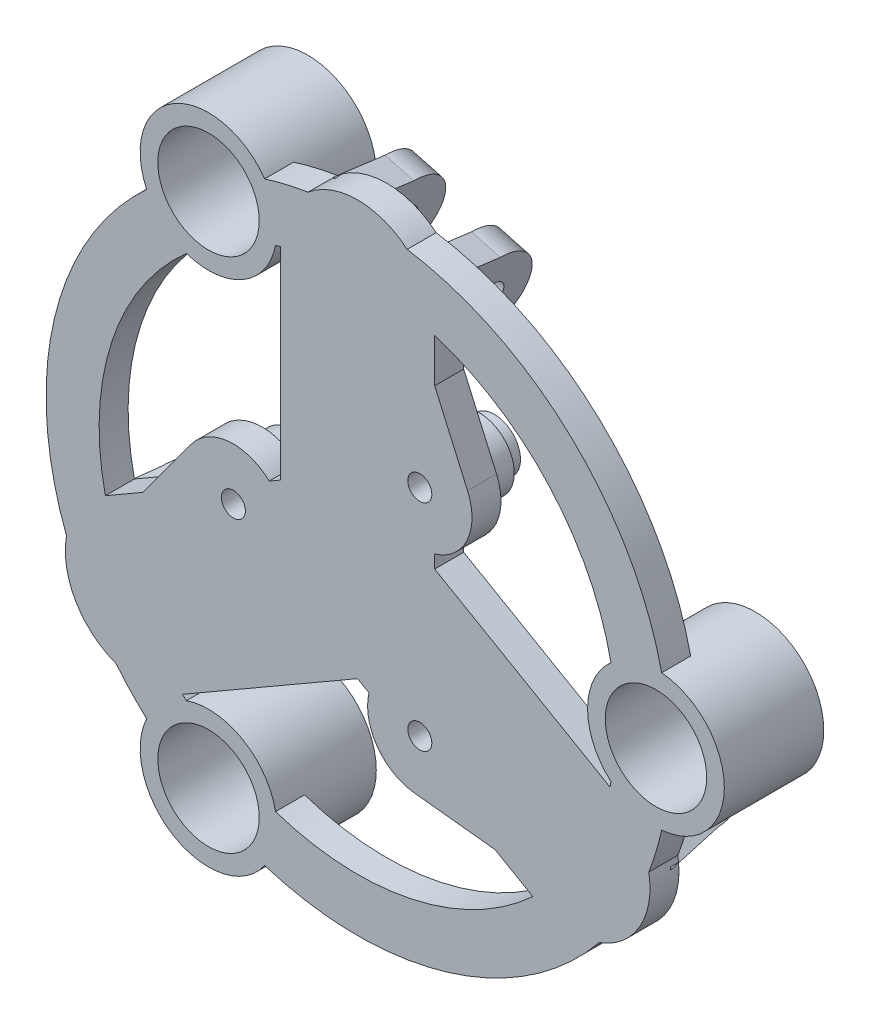
SolidWorks part; units mm, degrees
ref_plane "Front Plane" through (0, 0, 0) normal (0, 0, 1) x (1, 0, 0)
ref_plane "Top Plane" through (0, 0, 0) normal (0, 1, 0) x (1, 0, 0)
ref_plane "Right Plane" through (0, 0, 0) normal (1, 0, 0) x (0, 0, -1)
sketch "S01 - Joining centre of floating Y" plane through (0, 0, 0) normal (0, 0, 1) x (1, 0, 0)
  circle A0 centre (0, 0) radius 9
  dimension "D1" = 18
extrude "01 - Joining centre of floating Y" add sketch "S01 - Joining centre of floating Y" along normal blind 3.5 from offset 33.5
sketch "S02 - Floating spoke 1" plane through (0, 0, 0) normal (0, 0, 1) x (1, 0, 0)
  line L0 (4.65, -8.054) -> (-21.3308, -23.054)
  line L1 (-30.6308, -6.946) -> (-4.65, 8.054)
  arc A0 (-21.3308, -23.054) -> (-30.6308, -6.946) centre (-25.9808, -15) cw
  arc A1 (-4.65, 8.054) -> (4.65, -8.054) centre (0, 0) cw
  dimension "D1" = 9.3
  dimension "D2" = 9.3
  dimension "D3" = 4.65
  dimension "D4" = 4.65
  dimension "D5" = 21.3308
  dimension "D6" = 25.9808
  dimension "D7" = 30.6308
  dimension "D8" = 6.946
extrude "02 - Floating spoke 1" add sketch "S02 - Floating spoke 1" along normal blind 3.5 from offset 33.5
sketch "S03 - Floating spoke 2" plane through (0, 0, 0) normal (0, 0, 1) x (1, 0, 0)
  line L0 (4.65, 8.054) -> (30.6308, -6.946)
  line L1 (21.3308, -23.054) -> (-4.65, -8.054)
  arc A0 (30.6308, -6.946) -> (21.3308, -23.054) centre (25.9808, -15) cw
  arc A1 (-4.65, -8.054) -> (4.65, 8.054) centre (0, 0) cw
  dimension "D1" = 9.3
  dimension "D2" = 9.3
  dimension "D3" = 4.65
  dimension "D4" = 21.3308
  dimension "D5" = 25.9808
  dimension "D6" = 30.6308
  dimension "D7" = 4.65
  dimension "D8" = 6.946
extrude "03 - Floating spoke 2" add sketch "S03 - Floating spoke 2" along normal blind 3.5 from offset 33.5
sketch "S04 - Floating spoke 3" plane through (0, 0, 0) normal (0, 0, 1) x (1, 0, 0)
  line L0 (-9.3, 0) -> (-9.3, 30)
  line L1 (9.3, 30) -> (9.3, 0)
  arc A0 (-9.3, 30) -> (9.3, 30) centre (0, 30) cw
  arc A1 (9.3, 0) -> (-9.3, 0) centre (0, 0) cw
  dimension "D1" = 9.3
  dimension "D2" = 30
extrude "04 - Floating spoke 3" add sketch "S04 - Floating spoke 3" along normal blind 3.5 from offset 33.5
sketch "S05 - Moving tendon tie web 1" plane through (0, 0, 0) normal (0, 0, 1) x (1, 0, 0)
  line L0 (25.2997, -21.2631) -> (6.8189, -19.2535)
  line L1 (8.1811, -6.7273) -> (26.6618, -8.7369)
  arc A0 (6.8189, -19.2535) -> (8.1811, -6.7273) centre (7.5, -12.9904) cw
  arc A1 (26.6618, -8.7369) -> (25.2997, -21.2631) centre (25.9808, -15) cw
  dimension "D1" = 6.3
  dimension "D2" = 6.3
  dimension "D3" = 6.8189
  dimension "D4" = 7.5
  dimension "D5" = 8.1811
  dimension "D6" = 25.2997
  dimension "D7" = 25.9808
  dimension "D8" = 26.6618
  dimension "D9" = 6.7273
  dimension "D10" = 8.7369
extrude "05 - Moving tendon tie web 1" add sketch "S05 - Moving tendon tie web 1" along normal blind 3.5 from offset 33.5
sketch "S06 - Tendon anchor base 1" plane through (0, 0, 0) normal (0, 0, 1) x (1, 0, 0)
  circle A0 centre (7.5, -12.9904) radius 4.2
  dimension "D1" = 8.4
  dimension "D2" = 7.5
  dimension "D3" = 12.9904
extrude "06 - Tendon anchor base 1" add sketch "S06 - Tendon anchor base 1" along normal blind 3.7 from offset 29.8
sketch "S07 - Tendon mouth 1" plane through (0, 0, 0) normal (0, 0, 1) x (1, 0, 0)
  circle A0 centre (7.5, -12.9904) radius 3.15
  dimension "D1" = 6.3
  dimension "D2" = 7.5
  dimension "D3" = 12.9904
extrude "07 - Tendon mouth 1" add sketch "S07 - Tendon mouth 1" along normal blind 1.8 from offset 28
sketch "S08 - Moving tendon tie web 2" plane through (0, 0, 0) normal (0, 0, 1) x (1, 0, 0)
  line L0 (5.7645, 32.5417) -> (13.2645, 15.5321)
  line L1 (1.7355, 10.4487) -> (-5.7645, 27.4583)
  arc A0 (13.2645, 15.5321) -> (1.7355, 10.4487) centre (7.5, 12.9904) cw
  arc A1 (-5.7645, 27.4583) -> (5.7645, 32.5417) centre (0, 30) cw
  dimension "D1" = 6.3
  dimension "D2" = 6.3
  dimension "D3" = 1.7355
  dimension "D4" = 5.7645
  dimension "D5" = 7.5
  dimension "D6" = 13.2645
  dimension "D7" = 5.7645
  dimension "D8" = 10.4487
  dimension "D9" = 27.4583
extrude "08 - Moving tendon tie web 2" add sketch "S08 - Moving tendon tie web 2" along normal blind 3.5 from offset 33.5
sketch "S09 - Tendon anchor base 2" plane through (0, 0, 0) normal (0, 0, 1) x (1, 0, 0)
  circle A0 centre (7.5, 12.9904) radius 4.2
  dimension "D1" = 8.4
  dimension "D2" = 7.5
  dimension "D3" = 12.9904
extrude "09 - Tendon anchor base 2" add sketch "S09 - Tendon anchor base 2" along normal blind 3.7 from offset 29.8
sketch "S10 - Tendon mouth 2" plane through (0, 0, 0) normal (0, 0, 1) x (1, 0, 0)
  circle A0 centre (7.5, 12.9904) radius 3.15
  dimension "D1" = 6.3
  dimension "D2" = 7.5
  dimension "D3" = 12.9904
extrude "10 - Tendon mouth 2" add sketch "S10 - Tendon mouth 2" along normal blind 1.8 from offset 28
sketch "S11 - Moving tendon tie web 3" plane through (0, 0, 0) normal (0, 0, 1) x (1, 0, 0)
  line L0 (-31.0642, -11.2786) -> (-20.0835, 3.7214)
  line L1 (-9.9165, -3.7214) -> (-20.8973, -18.7214)
  arc A0 (-20.0835, 3.7214) -> (-9.9165, -3.7214) centre (-15, 0) cw
  arc A1 (-20.8973, -18.7214) -> (-31.0642, -11.2786) centre (-25.9808, -15) cw
  dimension "D1" = 6.3
  dimension "D2" = 6.3
  dimension "D3" = 9.9165
  dimension "D4" = 15
  dimension "D5" = 20.0835
  dimension "D6" = 20.8973
  dimension "D7" = 25.9808
  dimension "D8" = 31.0642
  dimension "D9" = 11.2786
extrude "11 - Moving tendon tie web 3" add sketch "S11 - Moving tendon tie web 3" along normal blind 3.5 from offset 33.5
sketch "S12 - Tendon anchor base 3" plane through (0, 0, 0) normal (0, 0, 1) x (1, 0, 0)
  circle A0 centre (-15, 0) radius 4.2
  dimension "D1" = 8.4
  dimension "D2" = 15
extrude "12 - Tendon anchor base 3" add sketch "S12 - Tendon anchor base 3" along normal blind 3.7 from offset 29.8
sketch "S13 - Tendon mouth 3" plane through (0, 0, 0) normal (0, 0, 1) x (1, 0, 0)
  circle A0 centre (-15, 0) radius 3.15
  dimension "D1" = 6.3
  dimension "D2" = 15
extrude "13 - Tendon mouth 3" add sketch "S13 - Tendon mouth 3" along normal blind 1.8 from offset 28
sketch "S14 - Joined drive hoop" plane through (0, 0, 0) normal (0, 0, 1) x (1, 0, 0)
  circle A0 centre (0, 0) radius 37.6
  circle A1 centre (0, 0) radius 31.2
  dimension "D1" = 62.4
  dimension "D2" = 75.2
extrude "14 - Joined drive hoop" add sketch "S14 - Joined drive hoop" along normal blind 3.5 from offset 33.5
sketch "S15 - Sliding guide barrel 1" plane through (0, 0, 0) normal (0, 0, 1) x (1, 0, 0)
  circle A0 centre (36, 0) radius 8.25
  dimension "D1" = 16.5
  dimension "D2" = 36
extrude "15 - Sliding guide barrel 1" add sketch "S15 - Sliding guide barrel 1" along normal blind 12 from offset 25
sketch "S16 - Sliding guide barrel 2" plane through (0, 0, 0) normal (0, 0, 1) x (1, 0, 0)
  circle A0 centre (-18, 31.1769) radius 8.25
  dimension "D1" = 16.5
  dimension "D2" = 18
  dimension "D3" = 31.1769
extrude "16 - Sliding guide barrel 2" add sketch "S16 - Sliding guide barrel 2" along normal blind 12 from offset 25
sketch "S17 - Sliding guide barrel 3" plane through (0, 0, 0) normal (0, 0, 1) x (1, 0, 0)
  circle A0 centre (-18, -31.1769) radius 8.25
  dimension "D1" = 16.5
  dimension "D2" = 18
  dimension "D3" = 31.1769
extrude "17 - Sliding guide barrel 3" add sketch "S17 - Sliding guide barrel 3" along normal blind 12 from offset 25
sketch "S18 - Guide bushing seats" plane through (0, 0, 0) normal (0, 0, 1) x (1, 0, 0)
  circle A0 centre (36, 0) radius 6.12
  circle A1 centre (-18, 31.1769) radius 6.12
  circle A2 centre (-18, -31.1769) radius 6.12
  dimension "D1" = 12.24
  dimension "D2" = 12.24
  dimension "D3" = 12.24
  dimension "D4" = 36
  dimension "D5" = 18
  dimension "D6" = 31.1769
  dimension "D7" = 31.1769
extrude "18 - Guide bushing seats" cut sketch "S18 - Guide bushing seats" along normal blind 14 from offset 24
sketch "S19 - Through tendon tie eyes" plane through (0, 0, 0) normal (0, 0, 1) x (1, 0, 0)
  circle A0 centre (7.5, -12.9904) radius 1.45
  circle A1 centre (7.5, 12.9904) radius 1.45
  circle A2 centre (-15, 0) radius 1.45
  dimension "D1" = 2.9
  dimension "D2" = 2.9
  dimension "D3" = 2.9
  dimension "D4" = 7.5
  dimension "D5" = 15
  dimension "D6" = 12.9904
  dimension "D7" = 12.9904
extrude "19 - Through tendon tie eyes" cut sketch "S19 - Through tendon tie eyes" along normal blind 10 from offset 27.8
sketch3d "Plane points - Integral B1 fork cheek L"
  point P0 (-25.9808, -15, 28)
  point P1 (-8.5941, -10.3413, 28)
  point P2 (-25.9808, -15, 10)
ref_plane "Drilling plane - Integral B1 fork cheek L" through (2.0096, -7.5, 0) normal (-0.2588, 0.9659, 0) x (0.9659, 0.2588, 0)
sketch "S20 - Integral B1 fork cheek L" plane through (2.0096, -7.5, 0) normal (-0.2588, 0.9659, 0) x (0.9659, 0.2588, 0)
  line L0 (-35.0778, -34.5) -> (-22.8778, -34.5)
  line L1 (-22.8778, -34.5) -> (-24.0278, -28)
  line L2 (-33.9278, -28) -> (-35.0778, -34.5)
  arc A0 (-24.0278, -28) -> (-33.9278, -28) centre (-28.9778, -28) ccw
  dimension "D1" = 4.95
  dimension "D2" = 22.8778
  dimension "D3" = 28.9778
  dimension "D4" = 35.0778
  dimension "D5" = 28
  dimension "D6" = 34.5
extrude "20 - Integral B1 fork cheek L" add sketch "S20 - Integral B1 fork cheek L" along normal blind 3.6 from offset 7.2 offset against normal yes
sketch3d "Plane points - Integral B1 fork cheek R"
  point P0 (-25.9808, -15, 28)
  point P1 (-8.5941, -10.3413, 28)
  point P2 (-25.9808, -15, 10)
ref_plane "Drilling plane - Integral B1 fork cheek R" through (2.0096, -7.5, 0) normal (-0.2588, 0.9659, 0) x (0.9659, 0.2588, 0)
sketch "S21 - Integral B1 fork cheek R" plane through (2.0096, -7.5, 0) normal (-0.2588, 0.9659, 0) x (0.9659, 0.2588, 0)
  line L0 (-35.0778, -34.5) -> (-22.8778, -34.5)
  line L1 (-22.8778, -34.5) -> (-24.0278, -28)
  line L2 (-33.9278, -28) -> (-35.0778, -34.5)
  arc A0 (-24.0278, -28) -> (-33.9278, -28) centre (-28.9778, -28) ccw
  dimension "D1" = 4.95
  dimension "D2" = 22.8778
  dimension "D3" = 28.9778
  dimension "D4" = 35.0778
  dimension "D5" = 28
  dimension "D6" = 34.5
extrude "21 - Integral B1 fork cheek R" add sketch "S21 - Integral B1 fork cheek R" along normal blind 3.6 from offset 3.6
sketch3d "Plane points - B1 pivot through both cheeks"
  point P0 (-25.9808, -15, 28)
  point P1 (-8.5941, -10.3413, 28)
  point P2 (-25.9808, -15, 10)
ref_plane "Drilling plane - B1 pivot through both cheeks" through (2.0096, -7.5, 0) normal (-0.2588, 0.9659, 0) x (0.9659, 0.2588, 0)
sketch "S22 - B1 pivot through both cheeks" plane through (2.0096, -7.5, 0) normal (-0.2588, 0.9659, 0) x (0.9659, 0.2588, 0)
  circle A0 centre (-28.9778, -28) radius 1.65
  dimension "D1" = 3.3
  dimension "D2" = 28.9778
  dimension "D3" = 28
extrude "22 - B1 pivot through both cheeks" cut sketch "S22 - B1 pivot through both cheeks" along normal blind 15 from offset 7.5 offset against normal yes
sketch3d "Plane points - B1 recessed pivot screw head"
  point P0 (-25.9808, -15, 28)
  point P1 (-8.5941, -10.3413, 28)
  point P2 (-25.9808, -15, 10)
ref_plane "Drilling plane - B1 recessed pivot screw head" through (2.0096, -7.5, 0) normal (-0.2588, 0.9659, 0) x (0.9659, 0.2588, 0)
sketch "S23 - B1 recessed pivot screw head" plane through (2.0096, -7.5, 0) normal (-0.2588, 0.9659, 0) x (0.9659, 0.2588, 0)
  circle A0 centre (-28.9778, -28) radius 2.7
  dimension "D1" = 5.4
  dimension "D2" = 28.9778
  dimension "D3" = 28
extrude "23 - B1 recessed pivot screw head" cut sketch "S23 - B1 recessed pivot screw head" along normal blind 1.5 from offset 7.3 offset against normal yes
sketch3d "Plane points - Integral B2 fork cheek L"
  point P0 (25.9808, -15, 28)
  point P1 (13.2528, -2.2721, 28)
  point P2 (25.9808, -15, 10)
ref_plane "Drilling plane - Integral B2 fork cheek L" through (5.4904, 5.4904, 0) normal (-0.7071, -0.7071, 0) x (0, 0, 1)
sketch "S24 - Integral B2 fork cheek L" plane through (5.4904, 5.4904, 0) normal (-0.7071, -0.7071, 0) x (0, 0, 1)
  line L0 (34.5, -35.0778) -> (34.5, -22.8778)
  line L1 (34.5, -22.8778) -> (28, -24.0278)
  line L2 (28, -33.9278) -> (34.5, -35.0778)
  arc A0 (28, -24.0278) -> (28, -33.9278) centre (28, -28.9778) ccw
  dimension "D1" = 4.95
  dimension "D2" = 28
  dimension "D3" = 34.5
  dimension "D4" = 22.8778
  dimension "D5" = 28.9778
  dimension "D6" = 35.0778
extrude "24 - Integral B2 fork cheek L" add sketch "S24 - Integral B2 fork cheek L" along normal blind 3.6 from offset 7.2 offset against normal yes
sketch3d "Plane points - Integral B2 fork cheek R"
  point P0 (25.9808, -15, 28)
  point P1 (13.2528, -2.2721, 28)
  point P2 (25.9808, -15, 10)
ref_plane "Drilling plane - Integral B2 fork cheek R" through (5.4904, 5.4904, 0) normal (-0.7071, -0.7071, 0) x (0, 0, 1)
sketch "S25 - Integral B2 fork cheek R" plane through (5.4904, 5.4904, 0) normal (-0.7071, -0.7071, 0) x (0, 0, 1)
  line L0 (34.5, -35.0778) -> (34.5, -22.8778)
  line L1 (34.5, -22.8778) -> (28, -24.0278)
  line L2 (28, -33.9278) -> (34.5, -35.0778)
  arc A0 (28, -24.0278) -> (28, -33.9278) centre (28, -28.9778) ccw
  dimension "D1" = 4.95
  dimension "D2" = 28
  dimension "D3" = 34.5
  dimension "D4" = 22.8778
  dimension "D5" = 28.9778
  dimension "D6" = 35.0778
extrude "25 - Integral B2 fork cheek R" add sketch "S25 - Integral B2 fork cheek R" along normal blind 3.6 from offset 3.6
sketch3d "Plane points - B2 pivot through both cheeks"
  point P0 (25.9808, -15, 28)
  point P1 (13.2528, -2.2721, 28)
  point P2 (25.9808, -15, 10)
ref_plane "Drilling plane - B2 pivot through both cheeks" through (5.4904, 5.4904, 0) normal (-0.7071, -0.7071, 0) x (0, 0, 1)
sketch "S26 - B2 pivot through both cheeks" plane through (5.4904, 5.4904, 0) normal (-0.7071, -0.7071, 0) x (0, 0, 1)
  circle A0 centre (28, -28.9778) radius 1.65
  dimension "D1" = 3.3
  dimension "D2" = 28
  dimension "D3" = 28.9778
extrude "26 - B2 pivot through both cheeks" cut sketch "S26 - B2 pivot through both cheeks" along normal blind 15 from offset 7.5 offset against normal yes
sketch3d "Plane points - B2 recessed pivot screw head"
  point P0 (25.9808, -15, 28)
  point P1 (13.2528, -2.2721, 28)
  point P2 (25.9808, -15, 10)
ref_plane "Drilling plane - B2 recessed pivot screw head" through (5.4904, 5.4904, 0) normal (-0.7071, -0.7071, 0) x (0, 0, 1)
sketch "S27 - B2 recessed pivot screw head" plane through (5.4904, 5.4904, 0) normal (-0.7071, -0.7071, 0) x (0, 0, 1)
  circle A0 centre (28, -28.9778) radius 2.7
  dimension "D1" = 5.4
  dimension "D2" = 28
  dimension "D3" = 28.9778
extrude "27 - B2 recessed pivot screw head" cut sketch "S27 - B2 recessed pivot screw head" along normal blind 1.5 from offset 7.3 offset against normal yes
sketch3d "Plane points - Integral B3 fork cheek L"
  point P0 (0, 30, 28)
  point P1 (-4.6587, 12.6133, 28)
  point P2 (0, 30, 10)
ref_plane "Drilling plane - Integral B3 fork cheek L" through (-7.5, 2.0096, 0) normal (0.9659, -0.2588, 0) x (0, 0, -1)
sketch "S28 - Integral B3 fork cheek L" plane through (-7.5, 2.0096, 0) normal (0.9659, -0.2588, 0) x (0, 0, -1)
  line L0 (-34.5, 35.0778) -> (-34.5, 22.8778)
  line L1 (-34.5, 22.8778) -> (-28, 24.0278)
  line L2 (-28, 33.9278) -> (-34.5, 35.0778)
  arc A0 (-28, 24.0278) -> (-28, 33.9278) centre (-28, 28.9778) ccw
  dimension "D1" = 4.95
  dimension "D2" = 28
  dimension "D3" = 34.5
  dimension "D4" = 22.8778
  dimension "D5" = 28.9778
  dimension "D6" = 35.0778
extrude "28 - Integral B3 fork cheek L" add sketch "S28 - Integral B3 fork cheek L" along normal blind 3.6 from offset 7.2 offset against normal yes
sketch3d "Plane points - Integral B3 fork cheek R"
  point P0 (0, 30, 28)
  point P1 (-4.6587, 12.6133, 28)
  point P2 (0, 30, 10)
ref_plane "Drilling plane - Integral B3 fork cheek R" through (-7.5, 2.0096, 0) normal (0.9659, -0.2588, 0) x (0, 0, -1)
sketch "S29 - Integral B3 fork cheek R" plane through (-7.5, 2.0096, 0) normal (0.9659, -0.2588, 0) x (0, 0, -1)
  line L0 (-34.5, 35.0778) -> (-34.5, 22.8778)
  line L1 (-34.5, 22.8778) -> (-28, 24.0278)
  line L2 (-28, 33.9278) -> (-34.5, 35.0778)
  arc A0 (-28, 24.0278) -> (-28, 33.9278) centre (-28, 28.9778) ccw
  dimension "D1" = 4.95
  dimension "D2" = 28
  dimension "D3" = 34.5
  dimension "D4" = 22.8778
  dimension "D5" = 28.9778
  dimension "D6" = 35.0778
extrude "29 - Integral B3 fork cheek R" add sketch "S29 - Integral B3 fork cheek R" along normal blind 3.6 from offset 3.6
sketch3d "Plane points - B3 pivot through both cheeks"
  point P0 (0, 30, 28)
  point P1 (-4.6587, 12.6133, 28)
  point P2 (0, 30, 10)
ref_plane "Drilling plane - B3 pivot through both cheeks" through (-7.5, 2.0096, 0) normal (0.9659, -0.2588, 0) x (0, 0, -1)
sketch "S30 - B3 pivot through both cheeks" plane through (-7.5, 2.0096, 0) normal (0.9659, -0.2588, 0) x (0, 0, -1)
  circle A0 centre (-28, 28.9778) radius 1.65
  dimension "D1" = 3.3
  dimension "D2" = 28
  dimension "D3" = 28.9778
extrude "30 - B3 pivot through both cheeks" cut sketch "S30 - B3 pivot through both cheeks" along normal blind 15 from offset 7.5 offset against normal yes
sketch3d "Plane points - B3 recessed pivot screw head"
  point P0 (0, 30, 28)
  point P1 (-4.6587, 12.6133, 28)
  point P2 (0, 30, 10)
ref_plane "Drilling plane - B3 recessed pivot screw head" through (-7.5, 2.0096, 0) normal (0.9659, -0.2588, 0) x (0, 0, -1)
sketch "S31 - B3 recessed pivot screw head" plane through (-7.5, 2.0096, 0) normal (0.9659, -0.2588, 0) x (0, 0, -1)
  circle A0 centre (-28, 28.9778) radius 2.7
  dimension "D1" = 5.4
  dimension "D2" = 28
  dimension "D3" = 28.9778
extrude "31 - B3 recessed pivot screw head" cut sketch "S31 - B3 recessed pivot screw head" along normal blind 1.5 from offset 7.3 offset against normal yes
